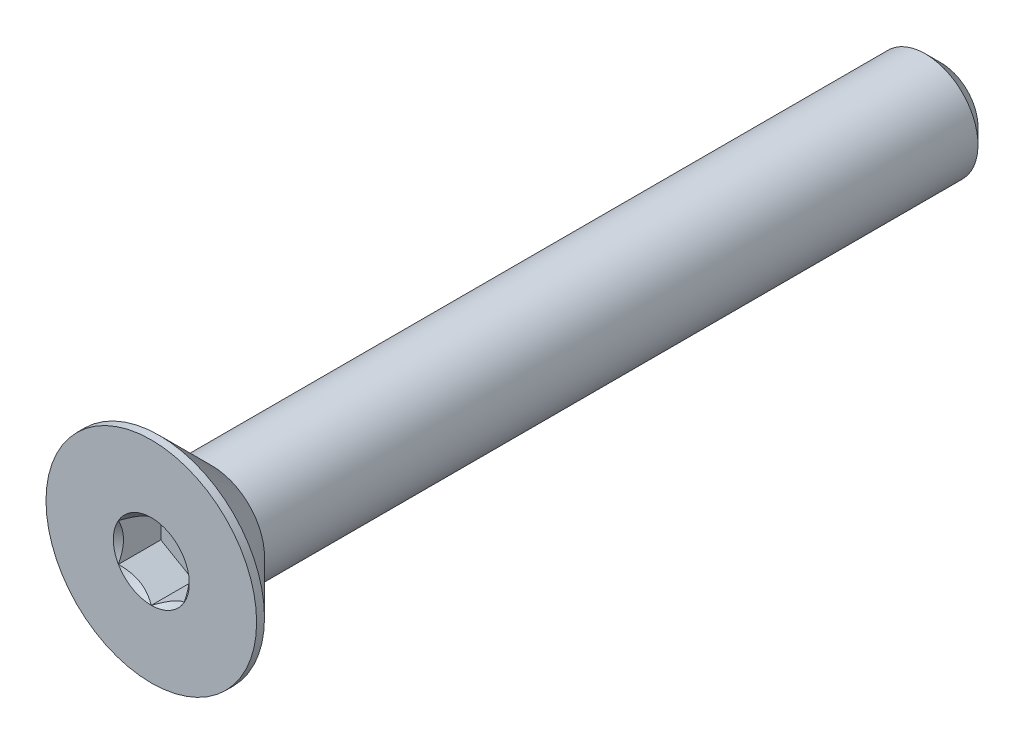
SolidWorks part; units mm, degrees
ref_plane "Front" through (0, 0, 0) normal (0, 0, 1) x (1, 0, 0)
ref_plane "Top" through (0, 0, 0) normal (0, 1, 0) x (1, 0, 0)
ref_plane "Right" through (0, 0, 0) normal (1, 0, 0) x (0, 0, -1)
sketch "Sketch1" plane through (0, 0, 0) normal (1, 0, 0) x (0, 0, -1)
  line L0 (-15, 4) -> (-14.7, 4) construction
  line L1 (-14.7, 4) -> (-12.7, 2) construction
  line L2 (-15, 2) -> (15, 2) construction
  line L3 (15, 2) -> (15, 0) construction
  line L4 (15, 0) -> (-15, 0) construction
  line L5 (-15, 0) -> (-15, 4) construction
  line L6 (-15, 4) -> (-15, -4) construction
  line L7 (15, 2) -> (15, -2) construction
  line L8 (-15, -4) -> (-14.7, -4) construction
  line L9 (-14.7, -4) -> (-12.7, -2) construction
  line L11 (-15, 2) -> (-15, 0) construction
  line L12 (-12.7, 2) -> (-12.7, 0) construction
  line L13 (14.9563, 2.0758) -> (15.3063, 1.4696) construction
  line L14 (15.3063, 1.4696) -> (15.6562, 2.0758) construction
  line L15 (15.6562, 2.0758) -> (14.9563, 2.0758) construction
  line L16 (15.3063, 2.0758) -> (15.3063, 2) construction
  line L17 (15.3063, 2) -> (15.3063, 1.5453) construction
  line L18 (15.3063, 1.5453) -> (15.3063, 1.4696) construction
  line L19 (15.3063, 2.0379) -> (15.6344, 2.0379) construction
  line L20 (15.3063, 2.0379) -> (14.9781, 2.0379) construction
  line L21 (15, 2) -> (15.6125, 2) construction
  line L22 (15.2625, 1.5453) -> (15.35, 1.5453) construction
  line L23 (15, -2) -> (-12.7, -2) construction
  point P10 (13.25, -2)
  point P24 (-12.7, 2)
  point P30 (0, 0)
  dimension "Head Diameter" = 8
  dimension "Head Height" = 2.3
  dimension "Length" = 30
  dimension "Countersink Angle" = 90
  dimension "Thread Pitch" = 0.7
  dimension "D2" = 0.0875
  dimension "Minimum Thread Length" = 27.7
  dimension "Thread Size" = 4
  dimension "D1" = 1.75
sketch "Sketch2" plane through (0, 0, 0) normal (0, 0, 1) x (1, 0, 0)
  line L1 (0, 1.4434) -> (-1.25, 0.7217) construction
  line L2 (-1.25, 0.7217) -> (-1.25, -0.7217) construction
  line L3 (-1.25, -0.7217) -> (0, -1.4434) construction
  line L4 (0, -1.4434) -> (1.25, -0.7217) construction
  line L5 (1.25, -0.7217) -> (1.25, 0.7217) construction
  line L6 (1.25, 0.7217) -> (0, 1.4434) construction
  circle A0 centre (0, 0) radius 1.25 construction
  dimension "Drive Size" = 2.5
sketch "Sketch3" plane through (0, 0, 0) normal (1, 0, 0) x (0, 0, -1)
  line L0 (-15, 2) -> (15, 2)
  line L1 (15, 2) -> (15, 0)
  line L2 (15, 0) -> (-15, 0)
  line L3 (-15, 0) -> (-15, 2)
revolve "Revolve1" add sketch "Sketch3" angle 360 about L4
chamfer "Chamfer1" distance 0.6 angle 45 1 edges at (0, 2, -15)
sketch "Sketch6" plane through (0, 0, 0) normal (1, 0, 0) x (0, 0, -1)
  line L0 (-15, 4) -> (-14.7, 4)
  line L1 (-14.7, 4) -> (-12.7, 2)
  line L2 (-12.7, 2) -> (-12.7, 0)
  line L3 (-12.7, 0) -> (-15, 0)
  line L4 (-15, 0) -> (-15, 4)
revolve "Revolve2" add sketch "Sketch6" angle 360 about L4
sketch "Sketch8" plane through (0, 0, 15) normal (0, 0, 1) x (1, 0, 0)
  line L0 (0, 1.4434) -> (-1.25, 0.7217) construction
  line L1 (1.25, 0.7217) -> (0, 1.4434) construction
  line L2 (1.25, -0.7217) -> (1.25, 0.7217) construction
  line L3 (0, -1.4434) -> (1.25, -0.7217) construction
  line L4 (-1.25, 0.7217) -> (-1.25, -0.7217) construction
  line L5 (-1.25, -0.7217) -> (0, -1.4434) construction
  line L6 (0, 1.4434) -> (-1.25, 0.7217)
  line L7 (1.25, 0.7217) -> (0, 1.4434)
  line L8 (1.25, -0.7217) -> (1.25, 0.7217)
  line L9 (0, -1.4434) -> (1.25, -0.7217)
  line L10 (-1.25, 0.7217) -> (-1.25, -0.7217)
  line L11 (-1.25, -0.7217) -> (0, -1.4434)
extrude "Cut-Extrude1" cut sketch "Sketch8" against normal blind 1.61
sketch "Sketch9" plane through (0, 0, 15) normal (0, 0, 1) x (1, 0, 0)
  circle A0 centre (0, 0) radius 1.4434
extrude "Cut-Extrude2" cut sketch "Sketch9" against normal up to next (1.61 mm away) draft 45
ref_plane "Plane1" [suppressed] through (0, 0, 12.7) normal (0, 0, 1) x (1, 0, 0)
split "Split1" [suppressed] bodies to split 124
sketch "Sketch4" [suppressed] plane through (0, 0, -15) normal (0, 0, -1) x (-1, 0, 0)
  circle A0 centre (0, 0) radius 2 construction
  circle A1 centre (0, 0) radius 2
curve "Helix/Spiral1" [suppressed] pitch 0.7 height 28.4 turns 40.5714
sketch "Sketch10" [suppressed] plane through (0, 0, 0) normal (1, 0, 0) x (0, 0, -1)
  line L0 (14.9781, 2.0379) -> (15.6344, 2.0379)
  line L1 (15.6344, 2.0379) -> (15.35, 1.5453)
  line L2 (15.35, 1.5453) -> (15.2625, 1.5453)
  line L3 (15.2625, 1.5453) -> (14.9781, 2.0379)
sweep "Cut-Sweep1" [suppressed] cut profiles "Sketch10" path "Helix/Spiral1"
equation "\"D2@Sketch1\" = \"Thread Pitch@Sketch1\" / 8"
equation "\"D4@Helix/Spiral1\"=\"Thread Pitch@Sketch1\""
equation "\"D3@Helix/Spiral1\"=\"Minimum Thread Length@Sketch1\"+\"Thread Pitch@Sketch1\""
equation "\"D1@Chamfer1\"=\"Thread Size@Sketch1\"*.15"
equation "\"D1@Cut-Extrude1\"=\"Head Height@Sketch1\"*.7"
equation "\"D1@Sketch1\"=\"Thread Pitch@Sketch1\"*2.5"
